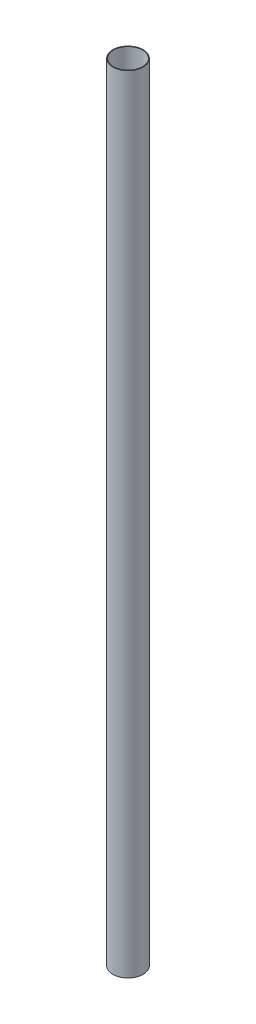
SolidWorks part; units mm, degrees
material "Stop 1060"
ref_plane "Płaszczyzna przednia" through (0, 0, 0) normal (0, 0, 1) x (1, 0, 0)
ref_plane "Płaszczyzna górna" through (0, 0, 0) normal (0, 1, 0) x (1, 0, 0)
ref_plane "Płaszczyzna prawa" through (0, 0, 0) normal (1, 0, 0) x (0, 0, -1)
sketch "Szkic1" plane through (0, 0, 0) normal (0, 1, 0) x (1, 0, 0)
  circle A0 centre (0, 0) radius 22.1
  circle A1 centre (0, 0) radius 23.1
  dimension "D1" = 44.2
  dimension "D2" = 46.2
extrude "Dodanie-wyciągnięcie1" add sketch "Szkic1" along normal blind 1200
